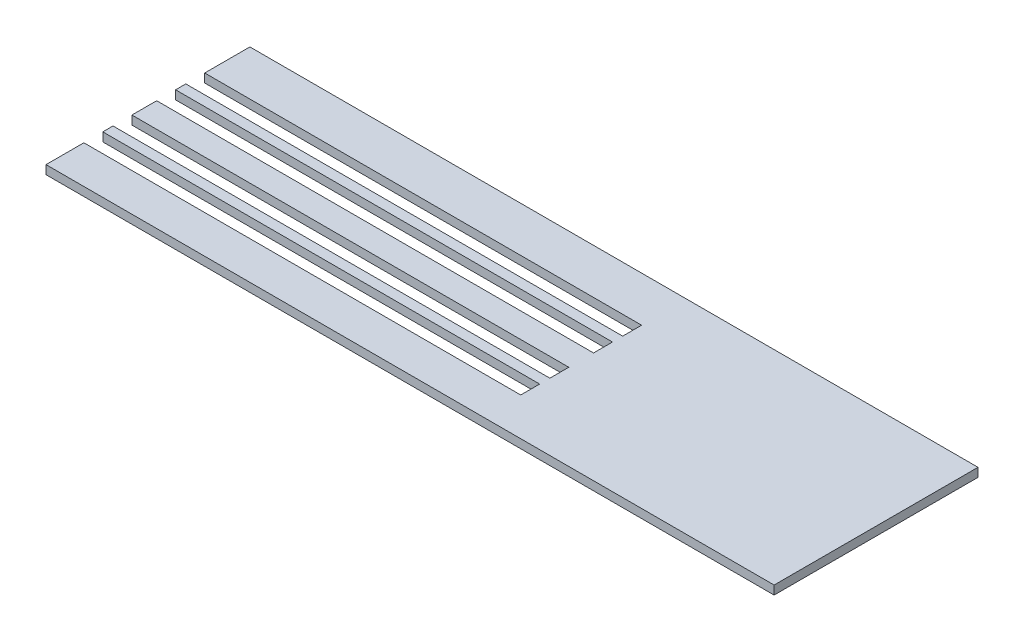
SolidWorks part; units mm, degrees
ref_plane "Front Plane" through (0, 0, 0) normal (0, 0, 1) x (1, 0, 0)
ref_plane "Top Plane" through (0, 0, 0) normal (0, 1, 0) x (1, 0, 0)
ref_plane "Right Plane" through (0, 0, 0) normal (1, 0, 0) x (0, 0, -1)
sketch "Sketch1" plane through (0, 0, 0) normal (0, 1, 0) x (1, 0, 0)
  line L0 (-150, 29.5) -> (0, 29.5)
  line L1 (0, 0) -> (100, 0)
  line L3 (-50, 70) -> (100, 70)
  line L4 (100, 0) -> (100, 70)
  line L5 (-150, 29.5) -> (-150, 38)
  line L6 (-150, 38) -> (0, 38)
  line L7 (0, 38) -> (0, 44.5)
  line L8 (0, 44.5) -> (-150, 44.5)
  line L9 (-150, 44.5) -> (-150, 48)
  line L10 (-150, 48) -> (0, 48)
  line L11 (0, 48) -> (0, 54.5)
  line L12 (0, 54.5) -> (-150, 54.5)
  line L13 (-150, 54.5) -> (-150, 70)
  line L14 (-150, 70) -> (-50, 70)
  line L16 (0, 29.5) -> (0, 23)
  line L17 (0, 23) -> (-150, 23)
  line L18 (-150, 23) -> (-150, 19.5)
  line L19 (-150, 19.5) -> (0, 19.5)
  line L20 (0, 19.5) -> (0, 13)
  line L21 (0, 13) -> (-150, 13)
  line L22 (-150, 13) -> (-150, 0)
  line L23 (-150, 0) -> (0, 0)
  dimension "D1" = 70
  dimension "D2" = 100
  dimension "D3" = 8.5
  dimension "D4" = 6.5
  dimension "D5" = 3.5
  dimension "D6" = 6.5
  dimension "D7" = 6.5
  dimension "D8" = 15.5
  dimension "D9" = 6.5
  dimension "D10" = 3.5
  dimension "D11" = 150
extrude "Boss-Extrude1" add sketch "Sketch1" along normal blind 3
ref_plane "Plane1" through (0, 0, -35) normal (0, 0, -1) x (-1, 0, 0)
